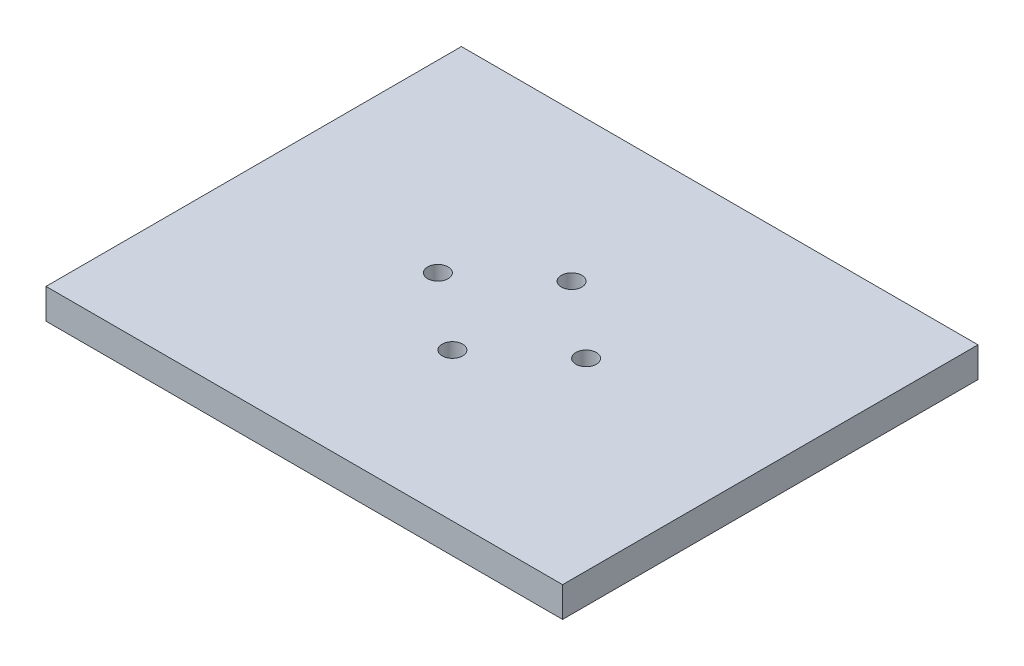
SolidWorks part; units mm, degrees
material "1060 Alloy"
ref_plane "Front Plane" through (0, 0, 0) normal (0, 0, 1) x (1, 0, 0)
ref_plane "Top Plane" through (0, 0, 0) normal (0, 1, 0) x (1, 0, 0)
ref_plane "Right Plane" through (0, 0, 0) normal (1, 0, 0) x (0, 0, -1)
sketch "Sketch1" plane through (0, 0, 0) normal (0, 1, 0) x (1, 0, 0)
  line L1 (57.825, 46.5) -> (-57.825, 46.5) construction
  line L2 (57.825, 46.5) -> (57.825, -46.5) construction
  line L3 (57.825, -46.5) -> (-57.825, -46.5) construction
  line L4 (-57.825, 46.5) -> (-57.825, -46.5) construction
  line L5 (-57.825, 46.5) -> (57.825, -46.5) construction
  line L6 (-57.825, 26.7384) -> (-42.825, 26.7384) construction
  line L36 (-42.825, 26.7384) -> (-9.5745, 0) construction
  line L37 (-9.5745, 0) -> (-42.825, -26.7384) construction
  line L38 (-42.825, -26.7384) -> (-57.825, -26.7384) construction
  line L39 (-57.825, -26.7384) -> (-57.825, -46.5) construction
  line L40 (-57.825, -46.5) -> (-33.2505, -46.5) construction
  line L41 (-33.2505, -46.5) -> (-33.2505, -34.4377) construction
  line L42 (-33.2505, -34.4377) -> (0, -7.6993) construction
  line L43 (0, -7.6993) -> (33.2505, -34.4377) construction
  line L44 (33.2505, -34.4377) -> (33.2505, -46.5) construction
  line L45 (33.2505, -46.5) -> (57.825, -46.5) construction
  line L46 (57.825, -46.5) -> (57.825, -26.7384) construction
  line L47 (57.825, -26.7384) -> (42.825, -26.7384) construction
  line L48 (42.825, -26.7384) -> (9.5745, 0) construction
  line L49 (9.5745, 0) -> (42.825, 26.7384) construction
  line L50 (42.825, 26.7384) -> (57.825, 26.7384) construction
  line L51 (57.825, 26.7384) -> (57.825, 46.5) construction
  line L52 (57.825, 46.5) -> (33.2505, 46.5) construction
  line L53 (33.2505, 46.5) -> (33.2505, 34.4377) construction
  line L54 (33.2505, 34.4377) -> (0, 7.6993) construction
  line L55 (0, 7.6993) -> (-33.2505, 34.4377) construction
  line L56 (-33.2505, 34.4377) -> (-33.2505, 46.5) construction
  line L57 (-33.2505, 46.5) -> (-57.825, 46.5) construction
  line L58 (-57.825, 46.5) -> (-57.825, 26.7384) construction
  line L59 (-57.825, -46.5) -> (57.825, 46.5) construction
  line L64 (42.825, 26.7384) -> (42.825, 34.4377)
  line L65 (42.825, 26.7384) -> (33.2505, 34.4377) construction
  line L66 (42.825, 34.4377) -> (33.2505, 34.4377)
  line L67 (33.2505, 34.4377) -> (-33.2505, 34.4377)
  line L68 (-33.2505, 34.4377) -> (-42.825, 34.4377)
  line L69 (-42.825, 34.4377) -> (-42.825, 26.7384)
  line L70 (-42.825, 26.7384) -> (-42.825, -26.7384)
  line L71 (-42.825, -26.7384) -> (-42.825, -34.4377)
  line L72 (-42.825, -34.4377) -> (-33.2505, -34.4377)
  line L73 (-33.2505, -34.4377) -> (33.2505, -34.4377)
  line L74 (33.2505, -34.4377) -> (42.825, -34.4377)
  line L75 (42.825, -34.4377) -> (42.825, -26.7384)
  line L78 (42.825, -26.7384) -> (42.825, 26.7384)
  circle A0 centre (0, -9.8808) radius 1.7
  circle A1 centre (0, 9.8808) radius 1.7
  circle A2 centre (12.2873, 0) radius 1.7
  circle A3 centre (-12.2873, 0) radius 1.7
  dimension "D5" = 3.4
  dimension "D6" = 3.4
  dimension "D7" = 3.4
  dimension "D8" = 3.4
  dimension "D1" = 115.65
  dimension "D2" = 93
  dimension "D3" = 12
  dimension "D4" = 15
extrude "Boss-Extrude1" add sketch "Sketch1" along normal blind 5
equation "\"L1L\"=500"
equation "\"L1Thick\"=6.35"
equation "\"Harm-Drive-Outer\"=74.5"
equation "\"L1-Spacing\"=115.65"
equation "\"L-Bracket-HoleToWall\"=12.5"
equation "\"L-Bracket-HoleToSide\"=11"
equation "\"Bracket-Hole-D\"=6.8"
equation "\"D1@Sketch1\"=\"L1-Spacing\""
